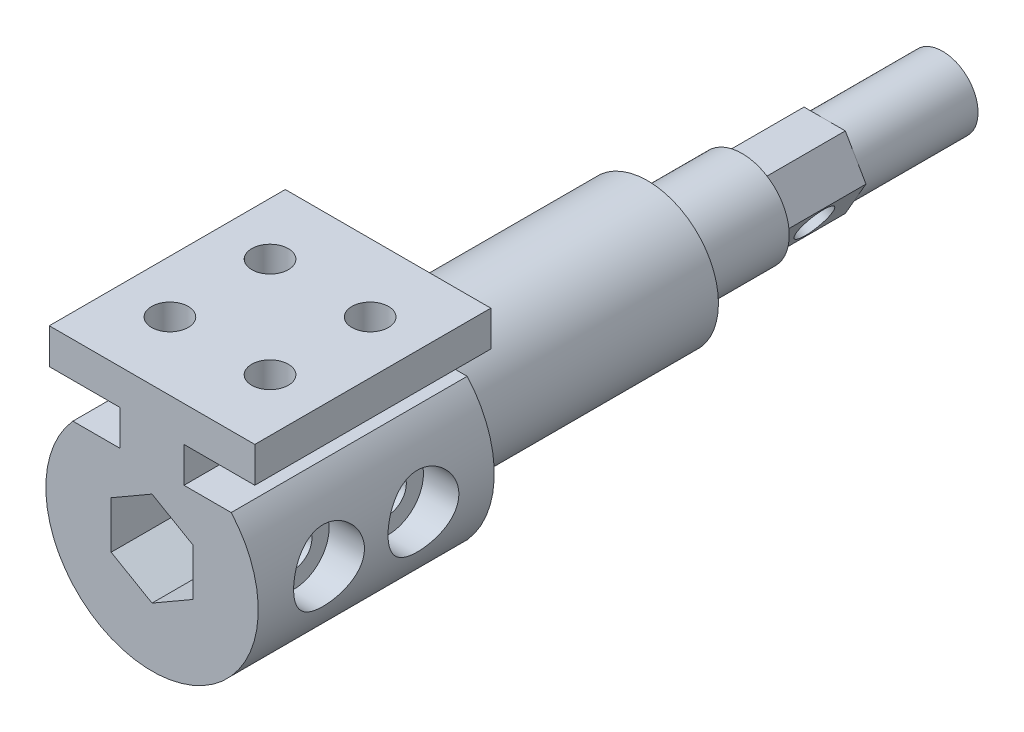
SolidWorks part; units mm, degrees
ref_plane "Front Plane" through (0, 0, 0) normal (0, 0, 1) x (1, 0, 0)
ref_plane "Top Plane" through (0, 0, 0) normal (0, 1, 0) x (1, 0, 0)
ref_plane "Right Plane" through (0, 0, 0) normal (1, 0, 0) x (0, 0, -1)
sketch "Sketch1" plane through (0, 0, 0) normal (0, 0, 1) x (1, 0, 0)
  line L0 (-3.4641, 2) -> (3.4641, -2) construction
  line L1 (0, -4) -> (0, 4) construction
  line L2 (-3.4641, -2) -> (3.4641, 2) construction
  line L15 (3.4641, 2) -> (3.4641, -2)
  line L16 (3.4641, -2) -> (0, -4)
  line L17 (0, -4) -> (-3.4641, -2)
  line L18 (-3.4641, -2) -> (-3.4641, 2)
  line L19 (-3.4641, 2) -> (0, 4)
  line L20 (0, 4) -> (3.4641, 2)
  line L21 (0, 0) -> (0, 6) construction
  line L22 (6.7082, 6) -> (-6.7082, 6) construction
  line L27 (-8.7082, 12) -> (8.7082, 12)
  line L32 (-8.7082, 12) -> (-8.7082, 9)
  line L36 (8.7082, 12) -> (8.7082, 9)
  line L40 (-6.7082, 6) -> (-2.7082, 6)
  line L41 (6.7082, 6) -> (2.7082, 6)
  line L42 (2.7082, 6) -> (2.7082, 9)
  line L43 (-2.7082, 6) -> (-2.7082, 9)
  line L44 (-2.7082, 9) -> (-8.7082, 9)
  line L45 (2.7082, 9) -> (8.7082, 9)
  circle A1 centre (0, 0) radius 4 construction
  arc A2 (-6.7082, 6) -> (6.7082, 6) centre (0, 0) ccw
  point P7 (0, 0)
  point P9 (0, 0)
  point P10 (0, 0)
  point P12 (0, 0)
  point P15 (0, 0)
  point P16 (0, 0)
  point P19 (0, 6)
  point P26 (0, 6)
extrude "Boss-Extrude1" add sketch "Sketch1" along normal blind 20
ref_plane "Plane4" through (0, 0, 0) normal (1, 0, 0) x (0, 0, -1)
sketch "Sketch8" plane through (0, 0, 0) normal (1, 0, 0) x (0, 0, -1)
  line L0 (0, 0) -> (-6, 0) construction
  line L1 (-14, 0) -> (-6, 0) construction
  circle A0 centre (-6, 0) radius 1.55
  circle A1 centre (-14, 0) radius 1.55
extrude "Cut-Extrude1" cut sketch "Sketch8" against normal blind 9 and the other way blind 9
sketch "Sketch11" plane through (0, 0, 0) normal (0, 0, -1) x (-1, 0, 0)
  circle A0 centre (0, 0) radius 6
extrude "Boss-Extrude12" add sketch "Sketch11" along normal blind 22
sketch "Sketch12" plane through (0, 0, -22) normal (0, 0, -1) x (-1, 0, 0)
  circle A0 centre (0, 0) radius 4
extrude "Boss-Extrude13" add sketch "Sketch12" along normal blind 8
sketch "Sketch13" plane through (0, 0, -30) normal (0, 0, -1) x (-1, 0, 0)
  line L0 (3.5, 0) -> (-3.5, 0) construction
  line L1 (-1.75, -3.0311) -> (1.75, 3.0311) construction
  line L2 (1.75, -3.0311) -> (-1.75, 3.0311) construction
  line L3 (1.75, 3.0311) -> (-1.75, 3.0311)
  line L4 (-1.75, 3.0311) -> (-3.5, 0)
  line L5 (-3.5, 0) -> (-1.75, -3.0311)
  line L6 (-1.75, -3.0311) -> (1.75, -3.0311)
  line L7 (1.75, -3.0311) -> (3.5, 0)
  line L8 (3.5, 0) -> (1.75, 3.0311)
  point P6 (0, 0)
  point P9 (0, 0)
  point P12 (0, 0)
extrude "Boss-Extrude14" add sketch "Sketch13" along normal blind 7 contours L4 L5 L6 L7 L8 L3
sketch "Sketch14" plane through (2.625, -1.5155, 0) normal (0.866, -0.5, 0) x (0, 0, -1)
  line L0 (30, 0) -> (37, 0) construction
  line L1 (30, 1.75) -> (30, -1.75) construction
  line L2 (37, 1.75) -> (37, -1.75) construction
  circle A0 centre (33.5, 0) radius 1.55
extrude "Cut-Extrude2" cut sketch "Sketch14" against normal blind 6.1
sketch "Sketch15" plane through (0, 0, -37) normal (0, 0, -1) x (-1, 0, 0)
  circle A0 centre (0, 0) radius 3
extrude "Boss-Extrude15" add sketch "Sketch15" along normal blind 10
sketch "Sketch16" plane through (0, 0, 0) normal (1, 0, 0) x (0, 0, -1)
  circle A1 centre (-6, 0) radius 3
  circle A2 centre (-14, 0) radius 3
extrude "Cut-Extrude5" cut sketch "Sketch16" against normal blind 3 from offset 9
extrude "Cut-Extrude6" cut sketch "Sketch16<2>" along normal blind 3 from offset 9 offset against normal yes
sketch "Sketch16<2>" plane through (0, 0, 0) normal (1, 0, 0) x (0, 0, -1) same geometry as "Sketch16"
sketch "Sketch17" plane through (0, 12, 0) normal (0, 1, 0) x (1, 0, 0)
  line L0 (-8.7082, 0) -> (8.7082, -20) construction
  line L1 (8.7082, 0) -> (-8.7082, -20) construction
  line L2 (-4.2426, -14.2426) -> (4.2426, -5.7574) construction
  line L3 (4.2426, -14.2426) -> (-4.2426, -5.7574) construction
  circle A0 centre (0, -10) radius 6 construction
  circle A1 centre (-4.2426, -5.7574) radius 1.55
  circle A2 centre (4.2426, -5.7574) radius 1.55
  circle A3 centre (4.2426, -14.2426) radius 1.55
  circle A4 centre (-4.2426, -14.2426) radius 1.55
  point P13 (0, -10)
  point P16 (0, -10)
  point P26 (0, -10)
  dimension "D1" = 4
extrude "Cut-Extrude7" cut sketch "Sketch17" against normal up to surface (3 mm away) up to face at (-5.7082, 9, 10)
